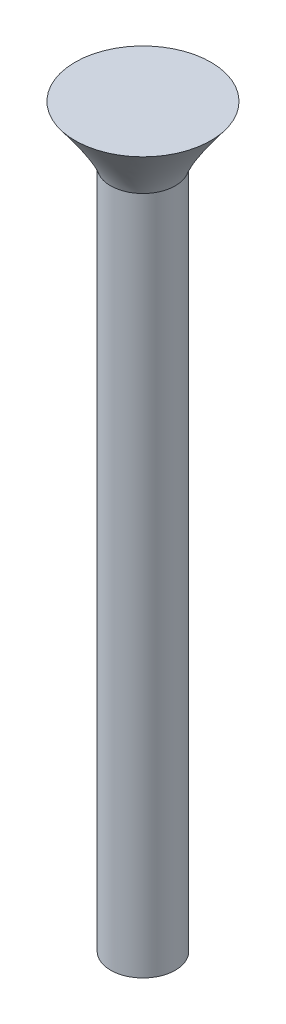
SolidWorks part; units mm, degrees
ref_plane "Front Plane" through (0, 0, 0) normal (0, 0, 1) x (1, 0, 0)
ref_plane "Top Plane" through (0, 0, 0) normal (0, 1, 0) x (1, 0, 0)
ref_plane "Right Plane" through (0, 0, 0) normal (1, 0, 0) x (0, 0, -1)
sketch "Sketch1" plane through (0, 0, 0) normal (0, 1, 0) x (1, 0, 0)
  circle A0 centre (0, 0) radius 0.9525
  dimension "D1" = 1.905
extrude "Boss-Extrude1" add sketch "Sketch1" along normal blind 20
ref_plane "Plane1" through (0, 21.6764, 0) normal (0, 1, 0) x (1, 0, 0)
sketch "Sketch2" plane through (0, 21.6764, 0) normal (0, 1, 0) x (1, 0, 0)
  circle A0 centre (0, 0) radius 2
  dimension "D1" = 4
sketch "Sketch3" plane through (0, 20, 0) normal (0, 1, 0) x (1, 0, 0)
  circle A1 centre (0, 0) radius 0.9525
  circle A2 centre (0, 0) radius 0.9525
  dimension "D1" = 0
loft "Loft1" add profiles "Sketch3", "Sketch2" connector at (-0.8681, 20, -0.392) connector at (-0.9013, 21.6764, -1.7854)
